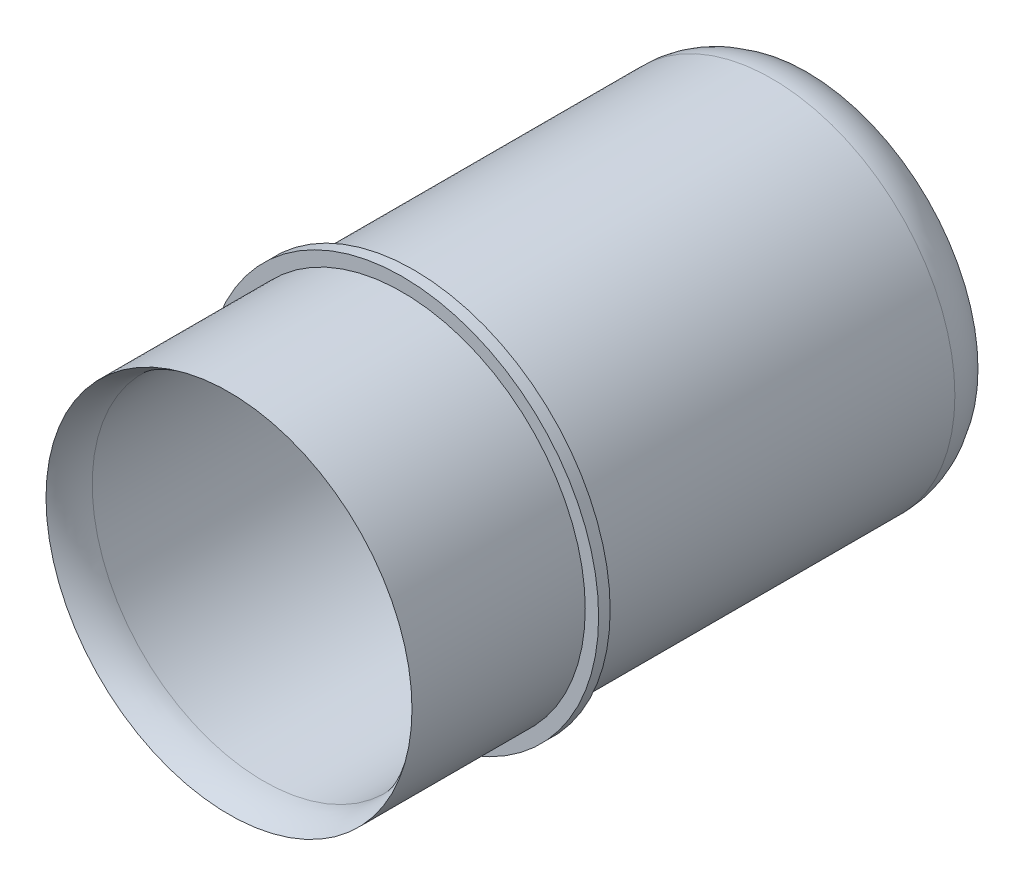
SolidWorks part; units mm, degrees
material "AISI 1020"
ref_plane "Front Plane" through (0, 0, 0) normal (0, 0, 1) x (1, 0, 0)
ref_plane "Top Plane" through (0, 0, 0) normal (0, 1, 0) x (1, 0, 0)
ref_plane "Right Plane" through (0, 0, 0) normal (1, 0, 0) x (0, 0, -1)
sketch "Sketch1" plane through (0, 0, 0) normal (0, 0, 1) x (1, 0, 0)
  circle A0 centre (0, 0) radius 31.685
  circle A1 centre (0, 0) radius 29.685
  dimension "D1" = 63.37
  dimension "D2" = 2
extrude "Boss-Extrude1" add sketch "Sketch1" along normal mid plane 100
ref_plane "Plane1" through (0, 0, 19) normal (0, 0, 1) x (1, 0, 0)
sketch "Sketch2" plane through (0, 0, 19) normal (0, 0, 1) x (1, 0, 0)
  circle A0 centre (0, 0) radius 29.685
  circle A1 centre (0, 0) radius 34
  circle A2 centre (0, 0) radius 29.685 construction
  dimension "D1" = 68
extrude "Boss-Extrude2" add sketch "Sketch2" along normal mid plane 2
fillet "Fillet1" radius 10 2 edges at (29.685, 0, 50) (31.685, 0, -50)
